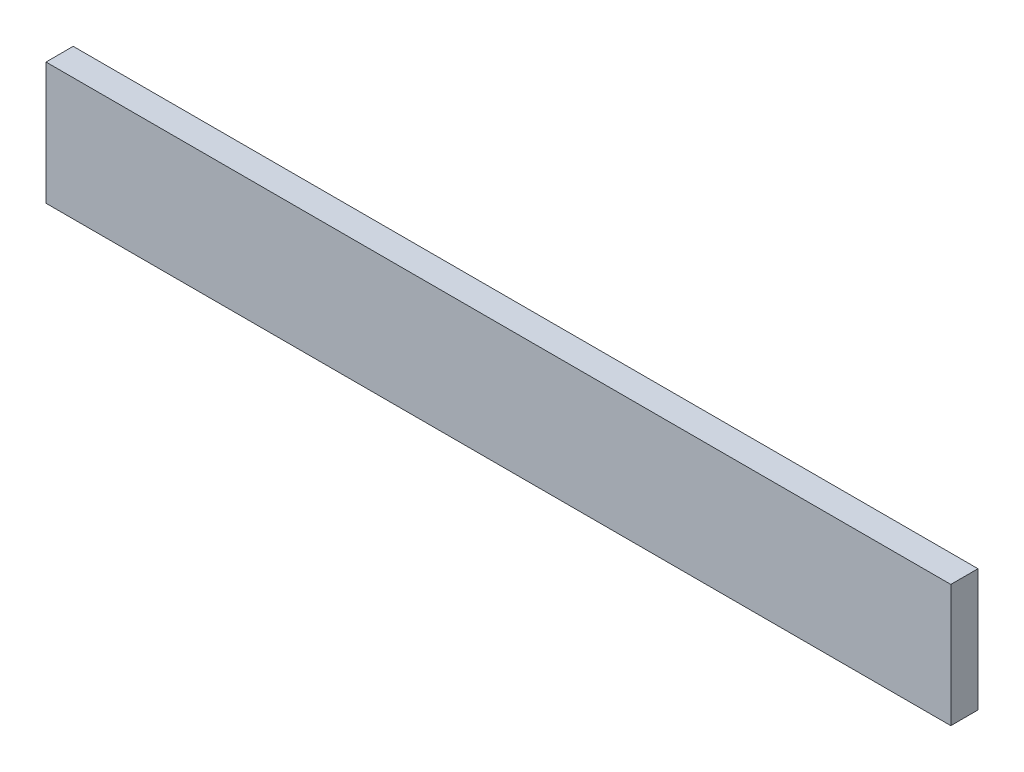
SolidWorks part; units mm, degrees
ref_plane "前视基准面" through (0, 0, 0) normal (0, 0, 1) x (1, 0, 0)
ref_plane "上视基准面" through (0, 0, 0) normal (0, 1, 0) x (1, 0, 0)
ref_plane "右视基准面" through (0, 0, 0) normal (1, 0, 0) x (0, 0, -1)
sketch "草图1" plane through (0, 0, 0) normal (0, 0, 1) x (1, 0, 0)
  line L0 (0, -5) -> (-166.4, -5)
  line L1 (21, -5) -> (-21, -5) construction
  line L2 (-166.4, 23.573) -> (-166.4, -96.427) construction
  line L3 (-166.4, -5) -> (-166.4, -50)
  line L4 (-166.4, -50) -> (166.4, -50)
  line L5 (166.4, 23.573) -> (166.4, -96.427) construction
  line L6 (166.4, -50) -> (166.4, -5)
  line L7 (166.4, -5) -> (0, -5)
  dimension "D1" = 45
extrude "凸台-拉伸1" add sketch "草图1" along normal blind 10
